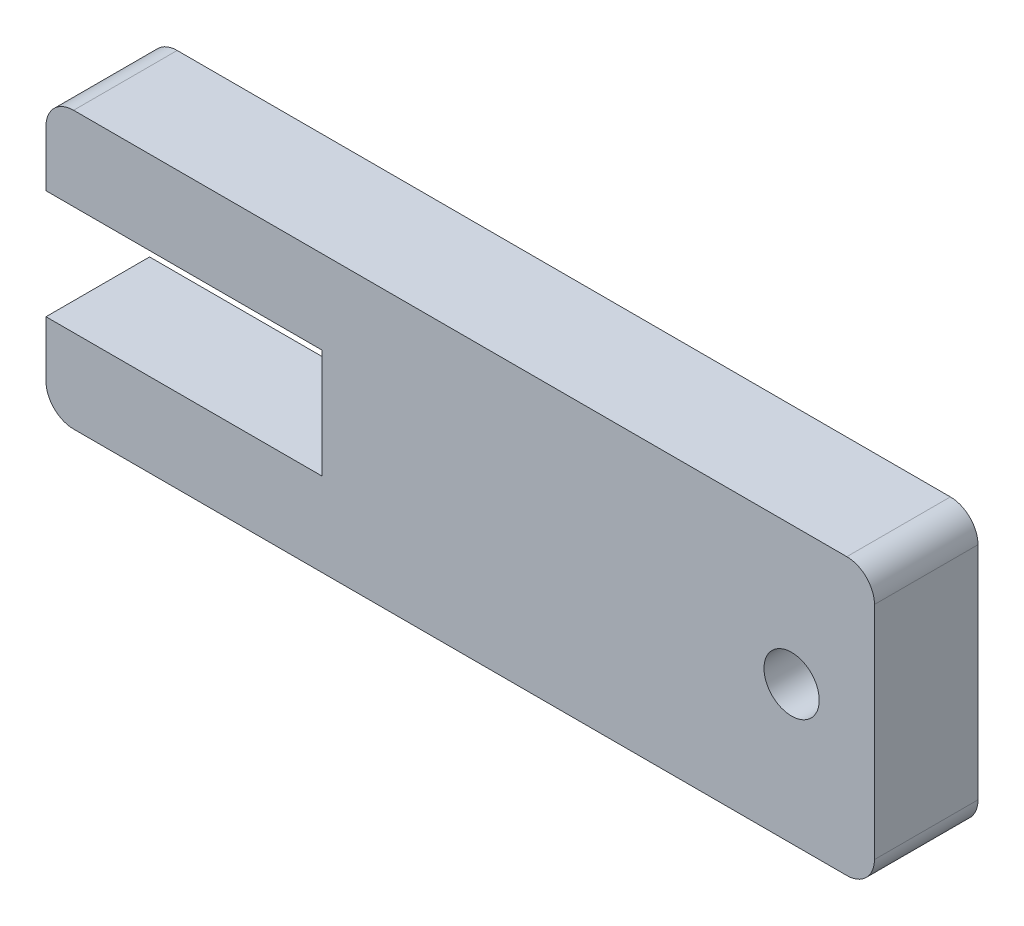
SolidWorks part; units mm, degrees
material "Corrugated Paper"
ref_plane "Front Plane" through (0, 0, 0) normal (0, 0, 1) x (1, 0, 0)
ref_plane "Top Plane" through (0, 0, 0) normal (0, 1, 0) x (1, 0, 0)
ref_plane "Right Plane" through (0, 0, 0) normal (1, 0, 0) x (0, 0, -1)
sketch "Sketch1" plane through (0, 0, 0) normal (0, 0, 1) x (1, 0, 0)
  line L0 (-12.7, 2.5082) -> (-12.7, 6.35)
  line L1 (-12.7, -2.5082) -> (0, -2.5082)
  line L3 (-12.7, 2.5082) -> (0, 2.5082)
  line L4 (0, -2.5082) -> (0, 2.5082)
  line L5 (-12.7, 6.35) -> (25.4, 6.35)
  line L6 (0, 0) -> (25.4, 0) construction
  line L7 (25.4, 6.35) -> (25.4, -6.35)
  line L8 (-12.7, -6.35) -> (25.4, -6.35)
  line L9 (-12.7, -2.5082) -> (-12.7, -6.35)
  dimension "D2" = 5.0165
  dimension "D3" = 25.4
  dimension "D4" = 12.7
extrude "Boss-Extrude1" add sketch "Sketch1" along normal mid plane 4.7625
fillet "Fillet1" radius 1.27 4 edges at (-12.7, -6.35, 0) (25.4, -6.35, 0) (25.4, 6.35, 0) (-12.7, 6.35, 0)
sketch "Sketch2" plane through (0, 0, 2.3813) normal (0, 0, 1) x (1, 0, 0)
  line L0 (0, 0) -> (25.4, 0) construction
  line L1 (25.4, -5.08) -> (25.4, 5.08) construction
  circle A0 centre (21.59, 0) radius 1.27
  dimension "D1" = 2.54
  dimension "D2" = 2.54
extrude "Cut-Extrude1" cut sketch "Sketch2" against normal through all
equation "\"D2@Sketch1\"=\"thick\"+\"clear\""
equation "\"D1@Sketch2\" = \"rodThick\""
equation "\"D1@Boss-Extrude1\"= \"thick\""
equation "\"rodThick\"= 0.1in"
equation "\"thick\"= 3/16in"
equation "\"clear\"= 0.01in"
